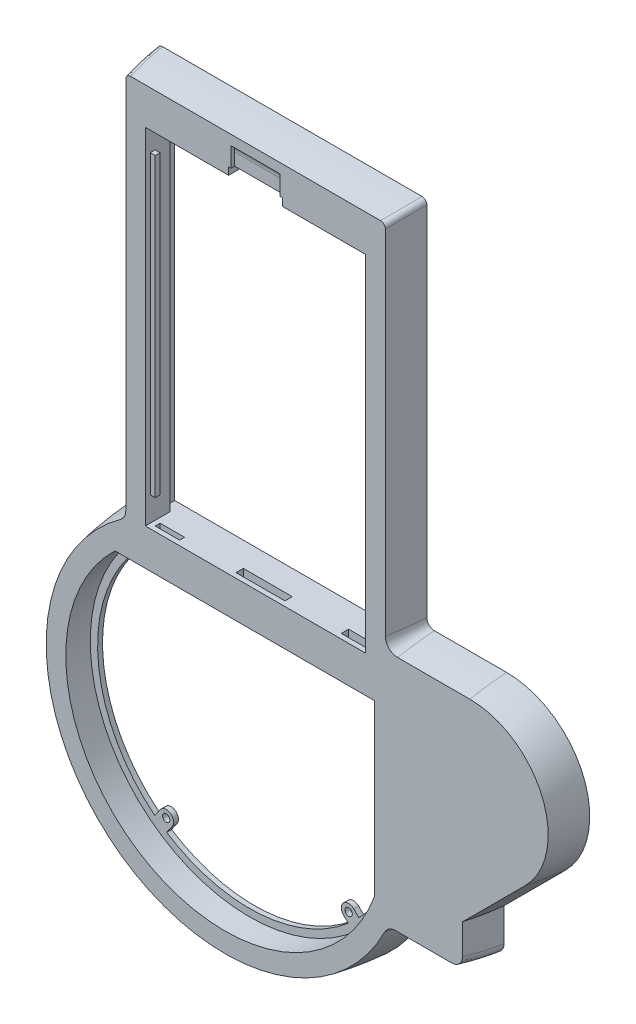
SolidWorks part; units mm, degrees
ref_plane "前视基准面" through (0, 0, 0) normal (0, 0, 1) x (1, 0, 0)
ref_plane "上视基准面" through (0, 0, 0) normal (0, 1, 0) x (1, 0, 0)
ref_plane "右视基准面" through (0, 0, 0) normal (1, 0, 0) x (0, 0, -1)
sketch "Sketch1" plane through (0, 0, 0) normal (0, 0, 1) x (1, 0, 0)
  line L0 (-10.9179, 60) -> (113.3582, 60) construction
  line L3 (-33.1662, 50) -> (-60, 50)
  line L4 (-60, 0) -> (-60, 50)
  line L6 (56.8821, -30) -> (90, -30)
  line L7 (90, -10.3553) -> (117.6777, 17.3223)
  line L13 (0, 60) -> (100, 60)
  line L14 (76, 5.7859) -> (76, -20.6668) construction
  line L16 (72, 20) -> (80, 20)
  line L17 (72, 20) -> (72, -20)
  line L18 (72, -20) -> (80, -20)
  line L19 (80, 20) -> (80, -20)
  line L20 (72, 20) -> (80, -20) construction
  line L21 (72, -20) -> (80, 20) construction
  line L25 (90, -30) -> (90, -10.3553)
  line L26 (56.8821, -30) -> (51.9615, -30)
  line L27 (57.5629, -26) -> (85.1685, -26) construction
  arc A0 (0, 60) -> (51.9615, -30) centre (0, 0) ccw
  circle A2 centre (0, 0) radius 10.5
  arc A8 (117.6777, 17.3223) -> (100, 60) centre (100, 35) ccw
  circle A9 centre (100, 35) radius 5
  circle A11 centre (69, -26) radius 1.5
  circle A12 centre (83, -26) radius 1.5
  point P21 (76, 0)
  dimension "D1" = 120
  dimension "D2" = 90
  dimension "D3" = 21
  dimension "D5" = 50
  dimension "D4" = 100
  dimension "D6" = 10
  dimension "D12" = 7
  dimension "D7" = 10
  dimension "D8" = 8
  dimension "D9" = 40
  dimension "D10" = 150
  dimension "D11" = 6
extrude "Boss-Extrude1" add sketch "Sketch1" along normal blind 2
sketch "Sketch2" plane through (0, 0, 2) normal (0, 0, 1) x (1, 0, 0)
  line L1 (-60, 0) -> (-60, 50) construction
  line L2 (0, 60) -> (100, 60) construction
  circle A1 centre (0, 0) radius 57
  circle A2 centre (60, 45) radius 2
  circle A6 centre (100, 35) radius 14
  dimension "D1" = 15
  dimension "D5" = 28
  dimension "D2" = 120
extrude "Cut-Extrude1" cut sketch "Sketch2" against normal up to next
sketch "Sketch3" plane through (0, 0, 0) normal (0, 0, -1) x (-1, 0, 0)
  line L4 (-30, 0) -> (-30, 80)
  line L5 (-30, 80) -> (5, 80)
  line L6 (5, 80) -> (5, 48)
  line L7 (5, 48) -> (25.3049, 16.1141)
  circle A2 centre (0, 0) radius 10.5
  arc A4 (-30, 0) -> (25.3049, 16.1141) centre (0, 0) ccw
  dimension "D1" = 80
  dimension "D2" = 35
  dimension "D3" = 32
extrude "Boss-Extrude2" add sketch "Sketch3" against normal blind 2
sketch "Sketch5" plane through (0, 0, 2) normal (0, 0, 1) x (1, 0, 0)
  line L0 (100, 48.4826) -> (100, 24.1919) construction
  line L1 (89.5844, 35) -> (110.5191, 35) construction
  circle A0 centre (92, 43) radius 2
  circle A1 centre (108, 43) radius 2
  circle A2 centre (108, 27) radius 2
  circle A3 centre (92, 27) radius 2
  dimension "D1" = 8
  dimension "D2" = 8
extrude "Cut-Extrude2" cut sketch "Sketch5" against normal blind 10
sketch "Sketch6" plane through (0, 0, 2) normal (0, 0, 1) x (1, 0, 0)
  line L0 (12.5, 60) -> (12.5, 200) construction
  line L1 (30, 80) -> (-5, 80) construction
  line L2 (12.5, 60) -> (55, 60)
  line L3 (-30, 60) -> (-30, 200)
  line L4 (-30, 200) -> (55, 200)
  line L5 (55, 60) -> (55, 200)
  line L6 (-30, 60) -> (55, 200) construction
  line L7 (-30, 200) -> (55, 60) construction
  line L8 (-30, 60) -> (-30, 51.9615)
  line L9 (12.5, 60) -> (-5, 60)
  line L10 (-5, 80) -> (-5, 59.7913) construction
  line L11 (-5, 60) -> (-5, 59.7913)
  arc A0 (-5, 59.7913) -> (-33.1662, 50) centre (0, 0) ccw construction
  arc A1 (-5, 59.7913) -> (-30, 51.9615) centre (0, 0) ccw
  point P2 (12.5, 130)
  point P10 (12.5, 80)
  dimension "D1" = 85
extrude "Boss-Extrude4" add sketch "Sketch6" against normal up to surface (2 mm away) up to face at (94, 27, 0)
sketch "Sketch7" plane through (0, 0, 2) normal (0, 0, 1) x (1, 0, 0)
  line L0 (55, 130) -> (-30, 130) construction
  line L1 (55, 60) -> (55, 200) construction
  line L2 (-30, 200) -> (-30, 51.9615) construction
  line L3 (12.5, 200) -> (12.5, 60) construction
  line L4 (55, 200) -> (-30, 200) construction
  circle A0 centre (-24, 194.5) radius 2
  circle A1 centre (49, 194.5) radius 2
  circle A2 centre (49, 65.5) radius 2
  circle A3 centre (-24, 65.5) radius 2
  circle A4 centre (-24, 130) radius 2
  circle A5 centre (49, 130) radius 2
  dimension "D1" = 4
  dimension "D2" = 4
  dimension "D3" = 6
  dimension "D4" = 5.5
  dimension "D5" = 5.5
  dimension "D6" = 6
extrude "Cut-Extrude3" cut sketch "Sketch7" against normal blind 10
sketch "Sketch8" plane through (0, 0, 2) normal (0, 0, 1) x (1, 0, 0)
  circle A0 centre (0, 0) radius 65
  circle A1 centre (0, 0) radius 10.5
extrude "Boss-Extrude5" add sketch "Sketch8" against normal up to surface (2 mm away) up to face at (51, 194.5, 0)
sketch "Sketch9" plane through (0, 0, 2) normal (0, 0, 1) x (1, 0, 0)
  line L0 (-60, 50) -> (-60, 25)
  line L1 (-60, 50) -> (-41.5331, 50)
  arc A0 (-41.5331, 50) -> (-60, 25) centre (0, 0) ccw
extrude "Cut-Extrude4" cut sketch "Sketch9" against normal blind 10
sketch "Sketch10" plane through (0, 0, 2) normal (0, 0, 1) x (1, 0, 0)
  line L0 (12.5, 200) -> (12.5, 60) construction
  line L1 (55, 200) -> (-30, 200) construction
  line L2 (55, 60) -> (100, 60) construction
  line L3 (-37.5, 210) -> (62.5, 210)
  line L4 (-37.5, 210) -> (-37.5, 60)
  line L5 (-37.5, 60) -> (62.5, 60)
  line L6 (62.5, 210) -> (62.5, 60)
  line L7 (-37.5, 210) -> (62.5, 60) construction
  line L8 (-37.5, 60) -> (62.5, 210) construction
  line L10 (-30, 200) -> (55, 200)
  line L11 (-30, 200) -> (-30, 60)
  line L12 (-30, 60) -> (55, 60)
  line L13 (55, 200) -> (55, 60)
  point P4 (12.5, 135)
  dimension "D1" = 100
  dimension "D2" = 150
extrude "Boss-Extrude6" add sketch "Sketch10" against normal blind 4 contours L4 L3 L6 L5 | L11 L10 L13 L12
sketch "Sketch11" plane through (0, 0, 2) normal (0, 0, 1) x (1, 0, 0)
  line L0 (-37.5, 60) -> (-37.5, 59.108)
  line L1 (-37.5, 60) -> (-36.0555, 60)
  line L2 (-30, 60) -> (-30, 57.6628)
  line L3 (-37.5, 60) -> (-30, 60) construction
  line L4 (-36.0555, 60) -> (-30, 60)
  line L5 (-30, 60) -> (-30, 57.6628)
  line L6 (63.2456, -30) -> (57.6628, -30)
  line L7 (90, -30) -> (57.6628, -30) construction
  arc A0 (-37.5, 59.108) -> (63.2456, -30) centre (0, 0) ccw
  arc A1 (-30, 57.6628) -> (57.6628, -30) centre (0, 0) ccw
  line M7 (-37.5, 60) -> (-30, 60)
  line M8 (-30, 60) -> (-30, 57.6628)
  arc M9 (-30, 57.6628) -> (57.6628, -30) centre (0, 0) ccw
  line M10 (57.6628, -30) -> (90, -30)
extrude "Boss-Extrude7" add sketch "Sketch11" against normal blind 4 contours L0 A0 M10 M9 M8 M7
sketch "Sketch12" plane through (0, 0, 2) normal (0, 0, 1) x (1, 0, 0)
  line L0 (95, -5.3553) -> (90, -10.3553)
  line L1 (62.5, 64) -> (100, 64)
  line L2 (94, -12.0122) -> (120.5061, 14.4939)
  line L4 (90, -10.3553) -> (117.6777, 17.3223) construction
  line L5 (90, -10.3553) -> (90, -30)
  line L6 (90, -30) -> (63.2456, -30)
  line L8 (97.8284, -8.1838) -> (94, -12.0122)
  line L9 (94, -12.0122) -> (94, -30)
  line L10 (90, -30) -> (94, -30)
  line L11 (62.5, 60) -> (100, 60)
  line L12 (62.5, 64) -> (62.5, 60)
  line L13 (92.8284, -13.1838) -> (120.5061, 14.4939) construction
  line L14 (94, -12.0122) -> (94, -34) construction
  line L16 (90, -10.3553) -> (117.6777, 17.3223)
  line L17 (94, -34) -> (63.2456, -34) construction
  arc A0 (120.5061, 14.4939) -> (100, 64) centre (100, 35) ccw
  arc A3 (117.6777, 17.3223) -> (100, 60) centre (100, 35) ccw construction
  arc A6 (117.6777, 17.3223) -> (100, 60) centre (100, 35) ccw
  dimension "D1" = 4
extrude "Boss-Extrude8" add sketch "Sketch12" against normal blind 4
sketch "Sketch13" plane through (0, 0, 2) normal (0, 0, 1) x (1, 0, 0)
  line L1 (0, 60) -> (100, 60)
  line L2 (56.8821, -30) -> (90, -30) construction
  line L3 (56.8821, -30) -> (51.9615, -30) construction
  line L4 (90, -30) -> (90, -10.3553) construction
  line L5 (90, -10.3553) -> (117.6777, 17.3223) construction
  line L6 (56.8821, -30) -> (90, -30)
  line L7 (63.2456, -30) -> (94, -30)
  line L8 (94, -30) -> (94, -12.0122)
  line L9 (94, -30) -> (94, -12.0122)
  line L10 (94, -12.0122) -> (120.5061, 14.4939)
  line L11 (62.5, 64) -> (62.5, 210)
  line L12 (62.5, 210) -> (-37.5, 210)
  line L13 (-37.5, 210) -> (-37.5, 59.108)
  line L14 (63.2456, -30) -> (94, -30)
  line L18 (62.5, 64) -> (62.5, 210)
  line L19 (62.5, 210) -> (-37.5, 210)
  line L20 (-37.5, 210) -> (-37.5, 59.108)
  line L21 (56.8821, -30) -> (51.9615, -30)
  line L22 (90, -30) -> (90, -10.3553)
  line L23 (90, -10.3553) -> (117.6777, 17.3223)
  line L30 (94, -12.0122) -> (120.5061, 14.4939)
  line L31 (100, 64) -> (62.5, 64)
  line L32 (100, 64) -> (62.5, 64)
  arc A0 (0, 60) -> (51.9615, -30) centre (0, 0) ccw construction
  arc A1 (0, 60) -> (51.9615, -30) centre (0, 0) ccw
  arc A2 (120.5061, 14.4939) -> (100, 64) centre (100, 35) ccw
  arc A3 (-37.5, 59.108) -> (63.2456, -30) centre (0, 0) ccw
  arc A5 (-37.5, 59.108) -> (63.2456, -30) centre (0, 0) ccw
  arc A6 (117.6777, 17.3223) -> (100, 60) centre (100, 35) ccw construction
  arc A7 (117.6777, 17.3223) -> (100, 60) centre (100, 35) ccw
  arc A10 (120.5061, 14.4939) -> (100, 64) centre (100, 35) ccw
  line M17 (63.2456, -30) -> (94, -30)
  circle M32 centre (92, 27) radius 2
  circle M33 centre (108, 27) radius 2
  circle M34 centre (108, 43) radius 2
  circle M35 centre (92, 43) radius 2
  circle M36 centre (60, 45) radius 2
  line M37 (72, 20) -> (80, 20)
  line M38 (80, 20) -> (80, -20)
  line M39 (80, -20) -> (72, -20)
  line M40 (72, -20) -> (72, 20)
  circle M41 centre (100, 35) radius 5
  circle M42 centre (69, -26) radius 1.5
  circle M43 centre (83, -26) radius 1.5
  circle M44 centre (0, 0) radius 10.5
  dimension "D1" = 0
extrude "Cut-Extrude5" cut sketch "Sketch13" against normal blind 4 contours L23 A7 L1 A1 L21 L6 L22 M17 M33 M35 M40 M37 M38 M39 M41 M43 M44 M42 M36 M34 M32 | M37 M40 M39 M38 | M35 | M34 | M41 | M33 | M32 | M36 | M44
sketch "Sketch14" plane through (0, 0, 2) normal (0, 0, 1) x (1, 0, 0)
  line L0 (94, -12.0122) -> (94, -30) construction
  line L1 (94, -12.0122) -> (120.5061, 14.4939) construction
  line L2 (62.5, 64) -> (100, 64) construction
  line L3 (94, -12.0122) -> (94, -30)
  line L4 (94, -12.0122) -> (120.5061, 14.4939)
  line L5 (62.5, 64) -> (100, 64)
  line L6 (60.5, 62) -> (60.5, 62)
  line L7 (60.5, 62) -> (60.5, 62)
  line L8 (60.5, 62) -> (60.5, 62)
  line L9 (60.5, 62) -> (60.5, 62)
  line L10 (60.5, 62) -> (60.5, 62)
  line L11 (60.5, 62) -> (60.5, 62)
  line L12 (60.5, 62) -> (60.5, 62)
  line L13 (60.5, 62) -> (100, 62)
  line L14 (92, -11.1838) -> (119.0919, 15.9081)
  line L15 (92, -11.1838) -> (92, -30)
  line L16 (60.5, 64) -> (60.5, 62)
  line L17 (92, -30) -> (94, -30)
  line L52 (60.5, 208) -> (-35.5, 208)
  line L53 (60.5, 64) -> (60.5, 208)
  line L54 (-35.5, 208) -> (-35.5, 57.9978)
  line L55 (60.5, 208) -> (-35.5, 208)
  line L56 (60.5, 64) -> (60.5, 208)
  line L57 (-35.5, 208) -> (-35.5, 57.9978)
  line L71 (62.5, 210) -> (62.5, 64) construction
  line L72 (-37.5, 210) -> (62.5, 210) construction
  line L73 (-37.5, 210) -> (-37.5, 59.108) construction
  line L77 (62.5, 210) -> (62.5, 64)
  line L78 (-37.5, 210) -> (62.5, 210)
  line L79 (-37.5, 210) -> (-37.5, 59.108)
  line L80 (63.2456, -30) -> (61.0246, -30)
  line L81 (56.8821, -30) -> (90, -30) construction
  arc A0 (120.5061, 14.4939) -> (100, 64) centre (100, 35) ccw construction
  arc A1 (120.5061, 14.4939) -> (100, 64) centre (100, 35) ccw
  arc A2 (60.5, 62) -> (60.5, 62) centre (60.5, 62) ccw
  arc A3 (60.5, 62) -> (60.5, 62) centre (60.5, 62) cw
  arc A4 (119.0919, 15.9081) -> (100, 62) centre (100, 35) ccw
  arc A19 (-35.5, 57.9978) -> (61.4385, -29.1429) centre (0, 0) ccw
  arc A20 (-35.5, 57.9978) -> (61.0246, -30) centre (0, 0) ccw
  arc A26 (-37.5, 59.108) -> (63.2456, -30) centre (0, 0) ccw construction
  arc A28 (-37.5, 59.108) -> (63.2456, -30) centre (0, 0) ccw
  dimension "D1" = 2
  dimension "D2" = 2
extrude "Boss-Extrude9" add sketch "Sketch14" along normal blind 35
sketch "Sketch15" plane through (0, 0, 2) normal (0, 0, 1) x (1, 0, 0)
  line L0 (12.5, 208) -> (12.5, 61.1759) construction
  line L1 (-35.5, 208) -> (60.5, 208) construction
  line L2 (0, 60) -> (100, 60) construction
  line L3 (-30, 200) -> (55, 200) construction
  line L4 (-30, 200) -> (-30, 60) construction
  line L5 (-30, 60) -> (55, 60) construction
  line L6 (55, 200) -> (55, 60) construction
  line L7 (-30, 200) -> (55, 60) construction
  line L8 (-30, 60) -> (55, 200) construction
  line L10 (-30, 203) -> (55, 203) construction
  line L11 (-30, 203) -> (-30, 67) construction
  line L12 (-30, 67) -> (55, 67) construction
  line L13 (55, 203) -> (55, 67) construction
  line L14 (-30, 203) -> (55, 67) construction
  line L15 (-30, 67) -> (55, 203) construction
  line L16 (-17.5, 64) -> (42.5, 64)
  line L17 (-17.5, 64) -> (-17.5, 61.7752)
  line L18 (-17.5, 61.7752) -> (42.5, 61.7752)
  line L19 (42.5, 64) -> (42.5, 61.7752)
  line L20 (-17.5, 64) -> (42.5, 61.7752) construction
  line L21 (-17.5, 61.7752) -> (42.5, 64) construction
  point P4 (12.5, 130)
  point P11 (12.5, 135)
  point P16 (12.5, 62.8876)
  dimension "D1" = 85
  dimension "D2" = 140
  dimension "D3" = 85
  dimension "D4" = 136
  dimension "D5" = 5
  dimension "D6" = 3
  dimension "D7" = 60
extrude "Boss-Extrude10" add sketch "Sketch15" along normal blind 35
sketch "Sketch16" plane through (0, 0, 2) normal (0, 0, 1) x (1, 0, 0)
  line L1 (-35.5, 208) -> (60.5, 208) construction
  line L2 (42.5, 64) -> (-17.5, 64) construction
  line L3 (-35.5, 208) -> (60.5, 208) construction
  line L4 (-15.5, 208) -> (-10.5, 208)
  line L5 (-15.5, 208) -> (-15.5, 163)
  line L6 (-15.5, 64) -> (-10.5, 64)
  line L7 (-10.5, 208) -> (-10.5, 163)
  line L8 (-17.5, 64) -> (-17.5, 61.7752) construction
  line L9 (10, 208) -> (15, 208)
  line L10 (10, 208) -> (10, 163)
  line L11 (10, 64) -> (15, 64)
  line L12 (15, 208) -> (15, 163)
  line L13 (35.5, 208) -> (40.5, 208)
  line L14 (35.5, 208) -> (35.5, 163)
  line L15 (35.5, 64) -> (40.5, 64)
  line L16 (40.5, 208) -> (40.5, 163)
  line L17 (42.5, 61.7752) -> (42.5, 64) construction
  line L18 (-35.5, 57.9978) -> (-35.5, 208) construction
  line L19 (-35.5, 163) -> (-15.5, 163)
  line L20 (-35.5, 163) -> (-35.5, 158)
  line L21 (-35.5, 158) -> (-15.5, 158)
  line L22 (60.5, 163) -> (60.5, 158)
  line L23 (60.5, 208) -> (60.5, 62) construction
  line L24 (60.5, 208) -> (60.5, 62) construction
  line L25 (-35.5, 114) -> (-15.5, 114)
  line L26 (-35.5, 114) -> (-35.5, 109)
  line L27 (-35.5, 109) -> (-15.5, 109)
  line L28 (60.5, 114) -> (60.5, 109)
  line L29 (-15.5, 158) -> (-15.5, 114)
  line L30 (-10.5, 158) -> (-10.5, 114)
  line L31 (-10.5, 163) -> (10, 163)
  line L32 (-10.5, 158) -> (10, 158)
  line L33 (12.5, 163) -> (35.5, 163)
  line L34 (15, 158) -> (35.5, 158)
  line L36 (10, 158) -> (10, 114)
  line L37 (15, 158) -> (15, 114)
  line L38 (35.5, 158) -> (35.5, 114)
  line L39 (40.5, 158) -> (40.5, 114)
  line L40 (40.5, 163) -> (60.5, 163)
  line L41 (40.5, 158) -> (60.5, 158)
  line L42 (40.5, 114) -> (60.5, 114)
  line L43 (40.5, 109) -> (60.5, 109)
  line L44 (-15.5, 109) -> (-15.5, 64)
  line L45 (-10.5, 109) -> (-10.5, 64)
  line L46 (10, 109) -> (10, 64)
  line L47 (15, 109) -> (15, 64)
  line L48 (35.5, 109) -> (35.5, 64)
  line L49 (40.5, 109) -> (40.5, 64)
  line L50 (-10.5, 114) -> (10, 114)
  line L51 (-10.5, 109) -> (10, 109)
  line L52 (15, 114) -> (35.5, 114)
  line L53 (15, 109) -> (35.5, 109)
  dimension "D9" = 45
  dimension "D1" = 5
  dimension "D2" = 5
  dimension "D4" = 5
  dimension "D5" = 2
  dimension "D6" = 2
  dimension "D7" = 5
  dimension "D8" = 5
  dimension "D10" = 45
extrude "Boss-Extrude12" add sketch "Sketch16" along normal blind 5
sketch "Sketch17" plane through (0, 0, 7) normal (0, 0, 1) x (1, 0, 0)
  line L0 (40.5, 163) -> (60.5, 163) construction
  line L1 (53.5, 163) -> (60.5, 163)
  line L2 (53.5, 163) -> (53.5, 158)
  line L3 (53.5, 158) -> (60.5, 158)
  line L4 (60.5, 163) -> (60.5, 158)
  line L5 (55, 200) -> (55, 60) construction
  line L6 (-35.5, 158) -> (-15.5, 158) construction
  line L7 (-35.5, 163) -> (-28.5, 163)
  line L8 (-35.5, 163) -> (-35.5, 158)
  line L9 (-35.5, 158) -> (-28.5, 158)
  line L10 (-28.5, 163) -> (-28.5, 158)
  line L11 (-35.5, 109) -> (-15.5, 109) construction
  line L12 (-35.5, 114) -> (-28.5, 114)
  line L13 (-35.5, 114) -> (-35.5, 109)
  line L14 (-35.5, 109) -> (-28.5, 109)
  line L15 (-28.5, 114) -> (-28.5, 109)
  line L16 (40.5, 114) -> (60.5, 114) construction
  line L17 (53.5, 114) -> (60.5, 114)
  line L18 (53.5, 114) -> (53.5, 109)
  line L19 (53.5, 109) -> (60.5, 109)
  line L20 (60.5, 114) -> (60.5, 109)
  line L21 (40.5, 109) -> (60.5, 109) construction
  line L22 (40.5, 109) -> (60.5, 109) construction
  line L23 (-30, 200) -> (-30, 60) construction
  line L24 (-10.5, 109) -> (-10.5, 64) construction
  line L25 (-15.5, 64) -> (-10.5, 64)
  line L26 (-15.5, 64) -> (-15.5, 69.5)
  line L27 (-15.5, 69.5) -> (-10.5, 69.5)
  line L28 (-10.5, 64) -> (-10.5, 69.5)
  line L29 (-30, 67) -> (55, 67) construction
  line L30 (10, 109) -> (10, 64) construction
  line L31 (10, 69.5) -> (15, 69.5)
  line L32 (10, 69.5) -> (10, 64)
  line L33 (10, 64) -> (15, 64)
  line L34 (15, 69.5) -> (15, 64)
  line L35 (35.5, 109) -> (35.5, 64) construction
  line L36 (35.5, 69.5) -> (40.5, 69.5)
  line L37 (35.5, 69.5) -> (35.5, 64)
  line L38 (35.5, 64) -> (40.5, 64)
  line L39 (40.5, 69.5) -> (40.5, 64)
  line L40 (-10.5, 208) -> (-10.5, 163) construction
  line L41 (-15.5, 208) -> (-10.5, 208)
  line L42 (-15.5, 208) -> (-15.5, 201.5)
  line L43 (-15.5, 201.5) -> (-10.5, 201.5)
  line L44 (-10.5, 208) -> (-10.5, 201.5)
  line L45 (-30, 203) -> (55, 203) construction
  line L46 (10, 208) -> (10, 163) construction
  line L47 (10, 201.5) -> (15, 201.5)
  line L48 (10, 201.5) -> (10, 208)
  line L49 (10, 208) -> (15, 208)
  line L50 (15, 201.5) -> (15, 208)
  line L51 (35.5, 208) -> (35.5, 163) construction
  line L52 (35.5, 201.5) -> (40.5, 201.5)
  line L53 (35.5, 201.5) -> (35.5, 208)
  line L54 (35.5, 208) -> (40.5, 208)
  line L55 (40.5, 201.5) -> (40.5, 208)
  dimension "D1" = 1.5
  dimension "D2" = 1.5
  dimension "D3" = 1.5
  dimension "D4" = 2.5
  dimension "D5" = 1.5
extrude "Boss-Extrude13" add sketch "Sketch17" along normal up to surface (30 mm away) up to face at (52.7768, 54.128, 37)
sketch "Sketch18" plane through (0, 109, 0) normal (0, -1, 0) x (1, 0, 0)
  line L0 (55.51, 37) -> (55.51, 9)
  line L1 (53.5, 37) -> (60.5, 37) construction
  line L2 (53.51, 7) -> (53.5, 7)
  line L3 (53.5, 37) -> (53.5, 7) construction
  line L4 (53.5, 7) -> (53.5, 37)
  line L5 (53.5, 37) -> (55.51, 37)
  arc A0 (55.51, 9) -> (53.51, 7) centre (53.51, 9) cw
  dimension "D2" = 2
  dimension "D1" = 2.01
extrude "Cut-Extrude6" cut sketch "Sketch18" against normal up to surface (54 mm away)
ref_plane "Plane1" through (12.5, 0, 0) normal (-1, 0, 0) x (0, 0, 1)
mirror "Mirror1" about plane through (12.5, 0, 0) normal (-1, 0, 0) of "Cut-Extrude6"
sketch "Sketch19" plane through (12.5, 0, 0) normal (-1, 0, 0) x (0, 0, 1)
  line L0 (37, 203.51) -> (9, 203.51)
  line L1 (37, 208) -> (37, 201.5) construction
  line L2 (7, 201.51) -> (7, 201.5)
  line L3 (37, 201.5) -> (7, 201.5) construction
  line L4 (37, 203.51) -> (37, 201.5)
  line L5 (37, 201.5) -> (7, 201.5)
  line L6 (37, 66.49) -> (10, 66.49)
  line L7 (37, 69.5) -> (37, 64) construction
  line L8 (7, 69.49) -> (7, 69.5)
  line L9 (37, 69.5) -> (7, 69.5) construction
  line L10 (37, 66.49) -> (37, 69.5)
  line L11 (37, 69.5) -> (7, 69.5)
  arc A0 (9, 203.51) -> (7, 201.51) centre (9, 201.51) ccw
  arc A1 (10, 66.49) -> (7, 69.49) centre (10, 69.49) cw
  dimension "D2" = 2
  dimension "D4" = 3
  dimension "D1" = 2.01
  dimension "D3" = 3.01
extrude "Cut-Extrude7" cut sketch "Sketch19" against normal mid plane 60
sketch "Sketch20" plane through (0, 0, 2) normal (0, 0, 1) x (1, 0, 0)
  line L0 (0, 0) -> (30, -51.9615) construction
  line L1 (0, 0) -> (-30, 51.9615) construction
  line L2 (0, 0) -> (-51.9615, -30) construction
  line L3 (103.8388, 3.4835) -> (92.5257, 14.7966) construction
  line L4 (90, -10.3553) -> (117.6777, 17.3223) construction
  line L5 (-23.3689, 52.4761) -> (-4.9075, 20.5001) construction
  line L6 (-33.7612, 46.4761) -> (-20.1962, 22.9808)
  line L7 (-23.3689, 52.4761) -> (-24.6535, 54.7011)
  line L8 (-23.3689, 52.4761) -> (-9.8038, 28.9808)
  line L9 (-33.7612, 46.4761) -> (-35.0458, 48.7011)
  line L10 (23.3689, -52.4761) -> (24.6535, -54.7011)
  line L11 (33.7612, -46.4761) -> (35.0458, -48.7011)
  line L12 (33.7612, -46.4761) -> (20.1962, -22.9808)
  line L13 (23.3689, -52.4761) -> (9.8038, -28.9808)
  line L14 (-51.6041, -22.8654) -> (-28.9808, -9.8038)
  line L15 (-45.6041, -33.2577) -> (-22.9808, -20.1962)
  line L16 (-51.6041, -22.8654) -> (-54.7011, -24.6535)
  line L17 (-45.6041, -33.2577) -> (-48.7011, -35.0458)
  line L18 (98.8884, 12.6754) -> (105.9599, 5.6045)
  line L23 (94.6468, 8.434) -> (101.7175, 1.3618)
  line L28 (101.7175, 1.3618) -> (105.9599, 5.6045)
  arc A0 (0, 60) -> (51.9615, -30) centre (0, 0) ccw construction
  arc A1 (-20.1962, 22.9808) -> (-9.8038, 28.9808) centre (-15, 25.9808) ccw
  arc A2 (-22.9808, -20.1962) -> (-28.9808, -9.8038) centre (-25.9808, -15) ccw
  arc A3 (20.1962, -22.9808) -> (9.8038, -28.9808) centre (15, -25.9808) ccw
  arc A5 (-35.0458, 48.7011) -> (-24.6535, 54.7011) centre (0, 0) cw
  arc A6 (24.6535, -54.7011) -> (35.0458, -48.7011) centre (0, 0) ccw
  arc A7 (-48.7011, -35.0458) -> (-54.7011, -24.6535) centre (0, 0) cw
  circle A8 centre (-15, 25.9808) radius 1.5
  circle A9 centre (-25.9808, -15) radius 1.5
  circle A10 centre (15, -25.9808) radius 1.5
  circle A11 centre (96.7678, 10.5546) radius 1.5
  arc A12 (98.8884, 12.6754) -> (94.6468, 8.434) centre (96.7678, 10.5546) ccw
  dimension "D1" = 30
  dimension "D2" = 30
  dimension "D3" = 30
  dimension "D4" = 10
  dimension "D5" = 6
extrude "Boss-Extrude14" add sketch "Sketch20" against normal blind 2
ref_plane "Plane2" through (0, 0, 37) normal (0, 0, 1) x (1, 0, 0)
sketch "Sketch21" plane through (0, 0, 37) normal (0, 0, 1) x (1, 0, 0)
  line L0 (119.0919, 15.9081) -> (92, -11.1838) construction
  line L1 (-37.5, 210) -> (62.5, 210)
  line L2 (-37.5, 210) -> (-37.5, 64)
  line L4 (62.5, 210) -> (62.5, 64)
  line L5 (119.0919, 15.9081) -> (92, -11.1838)
  line L6 (60.5, 62) -> (-37.5, 62)
  line L7 (-44.4553, 47) -> (103.3162, 47) construction
  line L8 (-49.1426, 47) -> (70.5, 47)
  line L9 (70.5, 47) -> (70.5, -20.9358)
  line L10 (70.5, -30) -> (63.2456, -30)
  line L11 (70.5, -30) -> (92, -30)
  line L12 (70.5, 47) -> (70.5, 62)
  line L13 (70.5, -20.9358) -> (90, -20.9358)
  line L14 (90, -30) -> (90, -10.3553) construction
  line L15 (61.0246, -30) -> (61.0246, 47)
  line L16 (70.5, 47) -> (124.1868, 47)
  line L20 (55.51, 62) -> (60.5, 62)
  line L21 (63.2456, -30) -> (92, -30)
  line L22 (90, -20.9358) -> (92, -20.9358)
  line L23 (-35.5, 62) -> (-35.5, 208)
  line L24 (-35.5, 208) -> (60.5, 208)
  line L25 (60.5, 208) -> (60.5, 62)
  line L46 (35.5, 203.51) -> (40.5, 203.51)
  line L47 (40.5, 203.51) -> (40.5, 208)
  line L48 (40.5, 208) -> (60.5, 208)
  line L49 (60.5, 208) -> (60.5, 163)
  line L50 (60.5, 163) -> (55.51, 163)
  line L51 (55.51, 163) -> (55.51, 158)
  line L52 (55.51, 158) -> (60.5, 158)
  line L53 (60.5, 158) -> (60.5, 114)
  line L54 (60.5, 114) -> (55.51, 114)
  line L55 (55.51, 114) -> (55.51, 109)
  line L56 (55.51, 109) -> (60.5, 109)
  line L57 (60.5, 109) -> (60.5, 62)
  line L58 (60.5, 62) -> (100, 62)
  line L59 (119.0919, 15.9081) -> (92, -11.1838)
  line L60 (92, -11.1838) -> (92, -30)
  line L61 (92, -30) -> (94, -30)
  line L62 (94, -30) -> (94, -12.0122)
  line L63 (94, -12.0122) -> (120.5061, 14.4939)
  line L64 (100, 64) -> (62.5, 64)
  line L65 (62.5, 64) -> (62.5, 210)
  line L66 (62.5, 210) -> (-37.5, 210)
  line L67 (-37.5, 210) -> (-37.5, 59.108)
  line L68 (63.2456, -30) -> (61.0246, -30)
  line L69 (-35.5, 57.9978) -> (-35.5, 109)
  line L70 (-35.5, 109) -> (-30.51, 109)
  line L72 (-30.51, 114) -> (-35.5, 114)
  line L73 (-35.5, 114) -> (-35.5, 158)
  line L74 (-35.5, 158) -> (-30.51, 158)
  line L75 (-30.51, 109) -> (-30.51, 114)
  line L76 (-30.51, 163) -> (-35.5, 163)
  line L77 (-35.5, 163) -> (-35.5, 208)
  line L78 (-35.5, 208) -> (-15.5, 208)
  line L79 (-15.5, 208) -> (-15.5, 203.51)
  line L81 (-10.5, 203.51) -> (-10.5, 208)
  line L82 (-10.5, 208) -> (10, 208)
  line L83 (10, 208) -> (10, 203.51)
  line L84 (-30.51, 158) -> (-30.51, 163)
  line L85 (15, 203.51) -> (15, 208)
  line L86 (15, 208) -> (35.5, 208)
  line L87 (35.5, 208) -> (35.5, 203.51)
  line L100 (60.5, 62) -> (100, 62)
  line L101 (119.0919, 15.9081) -> (92, -11.1838)
  line L102 (92, -11.1838) -> (92, -20.9358)
  line L103 (92, -30) -> (94, -30)
  line L104 (94, -30) -> (94, -12.0122)
  line L105 (94, -12.0122) -> (120.5061, 14.4939)
  line L106 (100, 64) -> (62.5, 64)
  line L107 (62.5, 64) -> (62.5, 210)
  line L108 (62.5, 210) -> (-37.5, 210)
  line L109 (-37.5, 210) -> (-37.5, 59.108)
  line L110 (63.2456, -30) -> (61.0246, -30)
  line L111 (-35.5, 57.9978) -> (-35.5, 62)
  line L150 (-15.5, 203.51) -> (-10.5, 203.51)
  line L152 (10, 203.51) -> (15, 203.51)
  arc A0 (-35.5, 57.9978) -> (61.0246, -30) centre (0, 0) ccw construction
  arc A1 (-35.5, 57.9978) -> (61.0246, -30) centre (0, 0) ccw
  arc A4 (119.0919, 15.9081) -> (100, 62) centre (100, 35) ccw
  arc A5 (120.5061, 14.4939) -> (100, 64) centre (100, 35) ccw
  arc A6 (-37.5, 59.108) -> (63.2456, -30) centre (0, 0) ccw
  arc A7 (-35.5, 57.9978) -> (61.0246, -30) centre (0, 0) ccw
  arc A8 (119.0919, 15.9081) -> (100, 62) centre (100, 35) ccw
  arc A9 (120.5061, 14.4939) -> (100, 64) centre (100, 35) ccw
  arc A10 (-37.5, 59.108) -> (63.2456, -30) centre (0, 0) ccw
  arc A11 (-35.5, 57.9978) -> (61.0246, -30) centre (0, 0) ccw
  dimension "D2" = 15
  dimension "D4" = 9.0642
  dimension "D1" = 0
extrude "Boss-Extrude15" add sketch "Sketch21" along normal blind 5
sketch "Sketch22" plane through (0, 0, 37) normal (0, 0, 1) x (1, 0, 0)
  line L1 (-84.8585, 214.4586) -> (151.8728, 214.4586)
  line L2 (-84.8585, 214.4586) -> (-84.8585, -77.374)
  line L3 (-84.8585, -77.374) -> (151.8728, -77.374)
  line L4 (151.8728, 214.4586) -> (151.8728, -77.374)
extrude "Cut-Extrude9" cut sketch "Sketch22" against normal up to next
sketch "Sketch24" plane through (0, 0, 42) normal (0, 0, 1) x (1, 0, 0)
  line L0 (61.0246, 47) -> (61.0246, -30)
  line L1 (70.5, 47) -> (120.7846, 47)
  line L2 (70.5, 47) -> (124.1868, 47) construction
  line L3 (70.5, 47) -> (70.5, -20.9358)
  line L4 (70.5, -20.9358) -> (90.4645, -20.9358)
  line L5 (70.5, -20.9358) -> (92, -20.9358) construction
  line L6 (94, -30) -> (63.2456, -30) construction
  line L7 (94, -30) -> (94, -12.0122) construction
  line L8 (94, -12.0122) -> (120.5061, 14.4939) construction
  line L9 (55.5, 203) -> (55.5, 62)
  line L10 (-30.5, 62) -> (-30.5, 203)
  line L11 (-30.5, 203) -> (55.5, 203)
  line L12 (55.5, 203) -> (55.5, 62)
  line L13 (-30.5, 62) -> (-30.5, 203)
  line L14 (-30.5, 203) -> (55.5, 203)
  line L15 (100, 64) -> (62.5, 64) construction
  line L16 (62.5, 210) -> (62.5, 64) construction
  line L17 (-37.5, 210) -> (62.5, 210) construction
  line L18 (-37.5, 210) -> (-37.5, 59.108) construction
  line L19 (94, -30) -> (63.2456, -30)
  line L20 (94, -30) -> (94, -12.0122)
  line L21 (94, -12.0122) -> (120.5061, 14.4939)
  line L22 (100, 64) -> (62.5, 64)
  line L23 (62.5, 210) -> (62.5, 64)
  line L24 (-37.5, 210) -> (62.5, 210)
  line L25 (-37.5, 210) -> (-37.5, 59.108)
  line L26 (-30.5, 62) -> (55.5, 62)
  line L27 (90.4645, -8.4767) -> (116.9706, 18.0294)
  line L28 (61.0246, 47) -> (-44.8999, 47)
  line L29 (-49.1426, 47) -> (61.0246, 47) construction
  line L30 (90.4645, -20.9358) -> (90.4645, -8.4767)
  arc A0 (-37.5, 59.108) -> (63.2456, -30) centre (0, 0) ccw construction
  arc A1 (120.5061, 14.4939) -> (100, 64) centre (100, 35) ccw construction
  arc A2 (-37.5, 59.108) -> (63.2456, -30) centre (0, 0) ccw
  arc A3 (120.5061, 14.4939) -> (100, 64) centre (100, 35) ccw
  arc A4 (-44.8999, 47) -> (58.728, -27.8571) centre (0, 0) ccw
  arc A5 (116.9706, 18.0294) -> (120.7846, 47) centre (100, 35) ccw
  arc A6 (-44.8999, 47) -> (61.0246, -22.383) centre (0, 0) ccw
  arc A7 (-34.8214, 54.886) -> (58.728, -27.8571) centre (0, 0) ccw construction
  arc A8 (116.9706, 18.0294) -> (100, 59) centre (100, 35) ccw construction
  line M13 (70.5, -20.9358) -> (70.5, 47)
  line M14 (70.5, 47) -> (124.1868, 47)
  arc M15 (124.1868, 47) -> (119.0919, 15.9081) centre (100, 35) cw
  line M16 (119.0919, 15.9081) -> (92, -11.1838)
  line M17 (92, -11.1838) -> (92, -20.9358)
  line M18 (92, -20.9358) -> (70.5, -20.9358)
  line M19 (60.5, 208) -> (60.5, 62)
  line M20 (60.5, 62) -> (-35.5, 62)
  line M21 (-35.5, 62) -> (-35.5, 208)
  line M22 (-35.5, 208) -> (60.5, 208)
  line M23 (61.0246, 47) -> (61.0246, -30)
  arc M24 (61.0246, -30) -> (-49.1426, 47) centre (0, 0) cw
  line M25 (-49.1426, 47) -> (61.0246, 47)
  arc M26 (-37.5, 59.108) -> (63.2456, -30) centre (0, 0) ccw
  line M27 (63.2456, -30) -> (94, -30)
  line M28 (94, -30) -> (94, -12.0122)
  line M29 (94, -12.0122) -> (120.5061, 14.4939)
  arc M30 (120.5061, 14.4939) -> (100, 64) centre (100, 35) ccw
  line M31 (100, 64) -> (62.5, 64)
  line M32 (62.5, 64) -> (62.5, 210)
  line M33 (62.5, 210) -> (-37.5, 210)
  line M34 (-37.5, 210) -> (-37.5, 59.108)
  dimension "D1" = 5
  dimension "D2" = 5
extrude "Boss-Extrude16" add sketch "Sketch24" along normal blind 10 contours L13 L14 L12 M20 M19 M22 M21 | L0 M34 M26 M27 M28 M29 M30 M31 M32 M33 M25 M23 M24 M22 M19 M20 M21 M18 M13 M14 M15 M16 M17 | A6 A4 L0 M25 M24 | A5 L27 L30 M18 M17 M16 M15 M14 | L25 A2 L19 L20 L21 A3 L22 L23 L24
sketch "Sketch25" plane through (0, 0, 52) normal (0, 0, 1) x (1, 0, 0)
  line L0 (12.5, 210) -> (12.5, 255.076) construction
  line L1 (62.5, 210) -> (-37.5, 210) construction
  line L2 (-2.5, 225) -> (-2.5, 210)
  line L3 (-2.5, 210) -> (27.5, 210)
  line L4 (27.5, 210) -> (27.5, 225)
  arc A0 (27.5, 225) -> (-2.5, 225) centre (12.5, 225) ccw
  dimension "D1" = 15
extrude "Boss-Extrude17" add sketch "Sketch25" against normal blind 6
sketch "Sketch31" plane through (0, 0, 52) normal (0, 0, 1) x (1, 0, 0)
  circle A0 centre (12.5, 225) radius 12.5
extrude "Cut-Extrude11" cut sketch "Sketch31" against normal blind 3.5
sketch "Sketch32" plane through (0, 0, 48.5) normal (0, 0, 1) x (1, 0, 0)
  circle A0 centre (12.5, 225) radius 7.5
extrude "Cut-Extrude12" cut sketch "Sketch32" against normal up to next
sketch "Sketch33" plane through (0, 0, 48.5) normal (0, 0, 1) x (1, 0, 0)
  line L0 (12.5, 225) -> (12.5, 240) construction
  arc A0 (27.5, 225) -> (-2.5, 225) centre (12.5, 225) ccw construction
  circle A1 centre (12.5, 235.5) radius 1.1
  dimension "D1" = 10.5
extrude "Cut-Extrude13" cut sketch "Sketch33" against normal blind 3
ref_plane "Plane3" through (12.5, 0, 0) normal (-1, 0, 0) x (0, 0, 1)
sketch "Sketch36" plane through (0, 0, 52) normal (0, 0, 1) x (1, 0, 0)
  line L0 (94, -30) -> (97, -30)
  line L1 (66.5507, -30) -> (63.2456, -30)
  line L75 (-37.5, 210) -> (-37.5, 59.108) construction
  line L76 (63.2456, -30) -> (94, -30) construction
  line L77 (94, -30) -> (94, -12.0122) construction
  line L78 (94, -12.0122) -> (120.5061, 14.4939) construction
  line L79 (100, 64) -> (62.5, 64) construction
  line L80 (62.5, 64) -> (62.5, 210) construction
  line L81 (62.5, 210) -> (27.5, 210) construction
  line L82 (27.5, 210) -> (27.5, 225) construction
  line L83 (-2.5, 225) -> (-2.5, 210) construction
  line L84 (-2.5, 210) -> (-37.5, 210) construction
  line L85 (65.1153, -33) -> (97, -33)
  line L86 (97, -33) -> (97, -13.2548)
  line L87 (97, -13.2548) -> (122.6274, 12.3726)
  line L88 (100, 67) -> (65.5, 67)
  line L89 (65.5, 67) -> (65.5, 213)
  line L90 (65.5, 213) -> (30.5, 213)
  line L91 (30.5, 213) -> (30.5, 225)
  line L92 (-5.5, 225) -> (-5.5, 213)
  line L93 (-5.5, 213) -> (-40.5, 213)
  line L94 (-40.5, 213) -> (-40.5, 60.7351)
  line L96 (97, -30) -> (97, -13.2548)
  line L97 (97, -13.2548) -> (122.6274, 12.3726)
  line L98 (100, 67) -> (65.5, 67)
  line L99 (65.5, 67) -> (65.5, 213)
  line L100 (65.5, 213) -> (30.5, 213)
  line L103 (-5.5, 213) -> (-40.5, 213)
  line L104 (-40.5, 213) -> (-40.5, 60.7351)
  line L105 (-37.5, 210) -> (-37.5, 59.108)
  line L106 (63.2456, -30) -> (66.5507, -30)
  line L107 (94, -30) -> (94, -12.0122)
  line L108 (94, -12.0122) -> (120.5061, 14.4939)
  line L109 (100, 64) -> (62.5, 64)
  line L110 (62.5, 64) -> (62.5, 210)
  line L111 (62.5, 210) -> (27.5, 210)
  line L112 (27.5, 210) -> (27.5, 213)
  line L113 (-2.5, 213) -> (-2.5, 210)
  line L114 (-2.5, 210) -> (-37.5, 210)
  line L115 (-5.5, 213) -> (-2.5, 213)
  line L116 (30.5, 213) -> (27.5, 213)
  arc A0 (-40.5, 60.7351) -> (66.5507, -30) centre (0, 0) ccw
  arc A16 (-37.5, 59.108) -> (63.2456, -30) centre (0, 0) ccw construction
  arc A17 (120.5061, 14.4939) -> (100, 64) centre (100, 35) ccw construction
  arc A19 (-40.5, 60.7351) -> (65.1153, -33) centre (0, 0) ccw
  arc A20 (122.6274, 12.3726) -> (100, 67) centre (100, 35) ccw
  arc A21 (30.5, 225) -> (-5.5, 225) centre (12.5, 225) ccw
  arc A22 (-40.5, 60.7351) -> (65.1153, -33) centre (0, 0) ccw
  arc A23 (122.6274, 12.3726) -> (100, 67) centre (100, 35) ccw
  arc A25 (-37.5, 59.108) -> (63.2456, -30) centre (0, 0) ccw
  arc A26 (120.5061, 14.4939) -> (100, 64) centre (100, 35) ccw
  line M28 (-37.5, 210) -> (-37.5, 59.108)
  arc M29 (-37.5, 59.108) -> (63.2456, -30) centre (0, 0) ccw
  line M30 (63.2456, -30) -> (94, -30)
  line M39 (-2.5, 225) -> (-2.5, 210)
  line M40 (-2.5, 210) -> (-37.5, 210)
  dimension "D1" = 3
extrude "Boss-Extrude19" add sketch "Sketch36" against normal up to surface (15 mm away) contours L104 A0 L115 L103 M30 M29 M28 M40 M39 | L96 L97 A23 L98 L99 L100 L116 L112 L111 L110 L109 A26 L108 L107 L0
fillet "Fillet1" radius 5 7 edges at (-40.5, 60.7351, 44.5) (65.5, 67, 44.5) (65.5, 213, 44.5) (-40.5, 213, 44.5) (27.5, 213, 49) (-2.5, 213, 49) (66.5507, -30, 44.5)
sketch "Sketch37" plane through (0, 0, 42) normal (0, 0, -1) x (-1, 0, 0)
  line L0 (-70.5, 47) -> (-70.5, -20.9358) construction
  line L1 (-70.5, -20.9358) -> (-92, -20.9358) construction
  line L2 (-90.4645, -20.9358) -> (-90.4645, -8.4767) construction
  line L3 (-90.4645, -8.4767) -> (-116.9706, 18.0294) construction
  line L4 (-70.5, 47) -> (-124.1868, 47) construction
  line L5 (-70.5, 47) -> (-70.5, -20.9358)
  line L6 (-70.5, -20.9358) -> (-90.4645, -20.9358)
  line L7 (-90.4645, -20.9358) -> (-90.4645, -8.4767)
  line L8 (-90.4645, -8.4767) -> (-116.9706, 18.0294)
  line L9 (-70.5, 47) -> (-120.7846, 47)
  arc A0 (-120.7846, 47) -> (-116.9706, 18.0294) centre (-100, 35) ccw construction
  arc A1 (-120.7846, 47) -> (-116.9706, 18.0294) centre (-100, 35) ccw
extrude "Boss-Extrude20" add sketch "Sketch37" against normal up to surface (10 mm away) up to face at (34.4039, 117.1063, 52)
sketch "Sketch38" plane through (0, 0, 37) normal (0, 0, -1) x (-1, 0, 0)
  line L1 (-27.5, 210) -> (2.5, 210)
  line L2 (-27.5, 210) -> (-27.5, 213)
  line L3 (-27.5, 213) -> (2.5, 213)
  line L4 (2.5, 210) -> (2.5, 213)
extrude "Boss-Extrude21" add sketch "Sketch38" against normal up to surface (9 mm away) up to face at (13.6, 235.5, 46)
ref_plane "Plane4" through (0, 0, 37) normal (0, 0, -1) x (-1, 0, 0)
sketch "Sketch39" plane through (0, 0, 37) normal (0, 0, -1) x (-1, 0, 0)
  line L7 (35.5, 213) -> (-60.5, 213)
  line L9 (35.5, 213) -> (-60.5, 213)
  line L11 (-65.5, 208) -> (-65.5, 72)
  line L13 (40.5, 63.3542) -> (40.5, 208)
  line L20 (40.5, 63.3542) -> (40.5, 208)
  line L21 (-65.5, 208) -> (-65.5, 72)
  line L22 (-70.5, 67) -> (-100, 67)
  line L23 (-70.5, 67) -> (-100, 67)
  line L25 (-122.6274, 12.3726) -> (-97, -13.2548)
  line L27 (-122.6274, 12.3726) -> (-97, -13.2548)
  line L29 (-97, -30) -> (-69.7065, -30)
  line L30 (-97, -30) -> (-69.7065, -30)
  line L31 (-97, -13.2548) -> (-97, -30)
  line L33 (-97, -13.2548) -> (-97, -30)
  arc A4 (-60.5, 213) -> (-65.5, 208) centre (-60.5, 208) ccw
  arc A9 (40.5, 208) -> (35.5, 213) centre (35.5, 208) ccw
  arc A12 (-60.5, 213) -> (-65.5, 208) centre (-60.5, 208) ccw
  arc A13 (-70.5, 67) -> (-65.5, 72) centre (-70.5, 72) ccw
  arc A14 (-70.5, 67) -> (-65.5, 72) centre (-70.5, 72) ccw
  arc A15 (-100, 67) -> (-122.6274, 12.3726) centre (-100, 35) ccw
  arc A16 (-65.2382, -32.7564) -> (42.5833, 59.293) centre (0, 0) ccw
  arc A17 (40.5, 63.3542) -> (42.5833, 59.293) centre (45.5, 63.3542) ccw
  arc A18 (40.5, 208) -> (35.5, 213) centre (35.5, 208) ccw
  arc A25 (-65.2382, -32.7564) -> (42.5833, 59.293) centre (0, 0) ccw
  arc A26 (40.5, 63.3542) -> (42.5833, 59.293) centre (45.5, 63.3542) ccw
  arc A27 (-100, 67) -> (-122.6274, 12.3726) centre (-100, 35) ccw
  arc A32 (-65.2382, -32.7564) -> (-69.7065, -30) centre (-69.7065, -35) ccw
  arc A33 (-65.2382, -32.7564) -> (-69.7065, -30) centre (-69.7065, -35) ccw
  dimension "D1" = 0
extrude "Boss-Extrude22" add sketch "Sketch39" along normal blind 39
ref_plane "Plane5" through (0, 0, 25) normal (0, 0, 1) x (1, 0, 0)
sketch "Sketch40" plane through (0, 0, 25) normal (0, 0, 1) x (1, 0, 0)
  line L7 (60.5, 213) -> (-35.5, 213)
  line L9 (60.5, 213) -> (-35.5, 213)
  line L11 (65.5, 72) -> (65.5, 208)
  line L13 (-40.5, 208) -> (-40.5, 63.3542)
  line L20 (-40.5, 208) -> (-40.5, 63.3542)
  line L21 (65.5, 72) -> (65.5, 208)
  line L22 (100, 67) -> (70.5, 67)
  line L23 (100, 67) -> (70.5, 67)
  line L25 (97, -13.2548) -> (122.6274, 12.3726)
  line L27 (97, -13.2548) -> (122.6274, 12.3726)
  line L29 (97, -30) -> (97, -13.2548)
  line L31 (69.7065, -30) -> (97, -30)
  line L32 (69.7065, -30) -> (97, -30)
  line L33 (97, -30) -> (97, -13.2548)
  arc A4 (65.5, 208) -> (60.5, 213) centre (60.5, 208) ccw
  arc A9 (-35.5, 213) -> (-40.5, 208) centre (-35.5, 208) ccw
  arc A12 (65.5, 208) -> (60.5, 213) centre (60.5, 208) ccw
  arc A13 (65.5, 72) -> (70.5, 67) centre (70.5, 72) ccw
  arc A14 (65.5, 72) -> (70.5, 67) centre (70.5, 72) ccw
  arc A15 (122.6274, 12.3726) -> (100, 67) centre (100, 35) ccw
  arc A16 (-42.5833, 59.293) -> (65.2382, -32.7564) centre (0, 0) ccw
  arc A17 (-42.5833, 59.293) -> (-40.5, 63.3542) centre (-45.5, 63.3542) ccw
  arc A18 (-35.5, 213) -> (-40.5, 208) centre (-35.5, 208) ccw
  arc A25 (-42.5833, 59.293) -> (65.2382, -32.7564) centre (0, 0) ccw
  arc A26 (-42.5833, 59.293) -> (-40.5, 63.3542) centre (-45.5, 63.3542) ccw
  arc A27 (122.6274, 12.3726) -> (100, 67) centre (100, 35) ccw
  arc A32 (69.7065, -30) -> (65.2382, -32.7564) centre (69.7065, -35) ccw
  arc A33 (69.7065, -30) -> (65.2382, -32.7564) centre (69.7065, -35) ccw
  dimension "D1" = 0
sketch "Sketch41" plane through (12.5, 0, 0) normal (-1, 0, 0) x (0, 0, 1)
  line L0 (-2, 213) -> (52, 213)
  arc A0 (-2, 213) -> (52, 213) centre (25, 65.45) cw
sweep "Sweep1" add profiles "Sketch41" path "Sketch40"
sketch "Sketch42" plane through (0, 0, 37) normal (0, 0, -1) x (-1, 0, 0)
  line L1 (118.0701, -89.7165) -> (-176.5446, -89.7165)
  line L2 (118.0701, -89.7165) -> (118.0701, 261.605)
  line L3 (118.0701, 261.605) -> (-176.5446, 261.605)
  line L4 (-176.5446, -89.7165) -> (-176.5446, 261.605)
extrude "Cut-Extrude16" cut sketch "Sketch42" along normal blind 39
sketch "Sketch43" plane through (12.5, 0, 0) normal (-1, 0, 0) x (0, 0, 1)
  line L0 (52, 213) -> (25.8111, 213) construction
  line L1 (37, 213) -> (46, 213) construction
  line L2 (37, 214.9692) -> (37, 208) construction
  line L3 (46, 213) -> (46, 213.9727)
  line L4 (46, 213.9727) -> (46, 215.1067)
  line L5 (46, 218) -> (46, 213.9727) construction
  line L6 (46, 215.1067) -> (37, 215.1067)
  line L7 (37, 215.1067) -> (37, 213)
  line L8 (37, 213) -> (46, 213)
extrude "Cut-Extrude17" cut sketch "Sketch43" against normal mid plane 30
fillet "Fillet2" radius 1 2 edges at (-2.5, 214.5389, 41.5075) (27.5, 214.5389, 41.5075)
fillet "Fillet3" radius 1 5 edges at (28.0381, 215.7435, 46) (27.5, 221.5, 46) (-3.0381, 215.7435, 46) (-2.5, 221.5, 46) (12.5, 240, 46)
ref_plane "Plane6" through (0, 0, 42) normal (0, 0, -1) x (-1, 0, 0)
sketch "Sketch44" plane through (0, 0, 42) normal (0, 0, -1) x (-1, 0, 0)
  line L0 (49.1426, 47) -> (-61.0246, 47) construction
  line L2 (38.8999, 42) -> (38.8999, 47)
  line L3 (44.0147, 39.8722) -> (50.1277, 45.9479)
  line L4 (38.8999, 47) -> (49.1426, 47)
  arc A0 (38.8999, 42) -> (44.0147, 39.8722) centre (41.8999, 42) ccw
  arc A2 (-61.0246, -30) -> (49.1426, 47) centre (0, 0) ccw construction
  circle A3 centre (41.8999, 42) radius 1.5
  arc A4 (50.1277, 45.9479) -> (49.1426, 47) centre (0, 0) ccw
  dimension "D1" = 5
  dimension "D2" = 3
extrude "Boss-Extrude23" add sketch "Sketch44" along normal blind 2
sketch "Sketch45" plane through (0, 0, 42) normal (0, 0, -1) x (-1, 0, 0)
  line L0 (44.8999, 47) -> (-61.0246, 47) construction
  line L1 (-61.0246, 47) -> (-61.0246, -22.383) construction
  line L2 (-53.0246, 42) -> (-53.0246, 47)
  line L3 (-56.0246, 39) -> (-61.0246, 39)
  line L4 (-61.0246, 39) -> (-61.0246, 47)
  line L5 (-61.0246, 47) -> (-53.0246, 47)
  arc A0 (-56.0246, 39) -> (-53.0246, 42) centre (-56.0246, 42) ccw
  circle A1 centre (-56.0246, 42) radius 1.5
  dimension "D1" = 5
  dimension "D2" = 5
extrude "Boss-Extrude24" add sketch "Sketch45" along normal blind 2
sketch "Sketch46" plane through (0, 0, 42) normal (0, 0, -1) x (-1, 0, 0)
  line L5 (35.5, 62) -> (-60.5, 62) construction
  line L6 (-70.5, 47) -> (-70.5, -20.9358) construction
  line L9 (-40.5, -43) -> (-44.6949, -47.1949) construction
  line L12 (-42.6213, -40.8787) -> (-48.9467, -47.204)
  line L13 (-38.3787, -45.1213) -> (-44.5936, -51.3362)
  line L14 (50.1277, 45.9479) -> (47.9981, 43.8313)
  line L15 (-61.0246, -22.383) -> (-61.0246, -30)
  line L16 (50.1277, 45.9479) -> (47.9981, 43.8313)
  arc A6 (-61.0246, -22.383) -> (47.9981, 43.8313) centre (0, 0) ccw construction
  arc A7 (-38.3787, -45.1213) -> (-42.6213, -40.8787) centre (-40.5, -43) ccw
  arc A8 (-61.0246, -30) -> (50.1277, 45.9479) centre (0, 0) ccw construction
  arc A9 (-61.0246, -22.383) -> (47.9981, 43.8313) centre (0, 0) ccw
  arc A10 (-61.0246, -30) -> (50.1277, 45.9479) centre (0, 0) ccw
  arc A12 (-47.8935, -48.2722) -> (-45.717, -50.3384) centre (0, 0) ccw
  arc A13 (-48.9467, -47.204) -> (-44.5936, -51.3362) centre (0, 0) ccw
  arc A14 (-43.5932, -48.2145) -> (47.9981, 43.8313) centre (0, 0) ccw
  circle A15 centre (-40.5, -43) radius 1.5
  dimension "D1" = 105
  dimension "D3" = 0
  dimension "D2" = 30
extrude "Boss-Extrude26" add sketch "Sketch46" along normal blind 2
sketch "Sketch47" plane through (0, 0, 42) normal (0, 0, -1) x (-1, 0, 0)
  line L0 (49.1426, 47) -> (-61.0246, 47) construction
  line L1 (-61.0246, -30) -> (-61.0246, 47) construction
  line L2 (31.5118, -48.7119) -> (37.2116, -56.9148)
  line L3 (36.4391, -45.2881) -> (42.0843, -53.4126)
  arc A0 (36.4391, -45.2881) -> (31.5118, -48.7119) centre (33.9754, -47) ccw
  arc A1 (-61.0246, -30) -> (49.1426, 47) centre (0, 0) ccw construction
  arc A2 (-44.5936, -51.3362) -> (50.1277, 45.9479) centre (0, 0) ccw construction
  arc A3 (37.2116, -56.9148) -> (42.0843, -53.4126) centre (0, 0) ccw
  circle A4 centre (33.9754, -47) radius 1.5
  dimension "D1" = 94
  dimension "D2" = 95
extrude "Boss-Extrude27" add sketch "Sketch47" along normal blind 2
sketch "Sketch48" plane through (0, 0, 42) normal (0, 0, -1) x (-1, 0, 0)
  line L0 (-61.0246, -30) -> (-61.0246, 47) construction
  line L1 (49.1426, 47) -> (-61.0246, 47) construction
  line L2 (-61.0246, -30) -> (-61.0246, 39)
  line L3 (38.8999, 47) -> (-53.0246, 47)
  line L4 (38.8999, 44) -> (-53.0246, 44)
  line L5 (-58.0246, -21.8437) -> (-58.0246, 39)
  line L6 (-53.0246, 47) -> (-53.0246, 44)
  line L7 (-53.0246, 42) -> (-53.0246, 47) construction
  line L8 (-61.0246, 39) -> (-58.0246, 39)
  line L9 (-61.0246, 39) -> (-56.0246, 39) construction
  line L10 (38.8999, 47) -> (38.8999, 44)
  line L11 (38.8999, 47) -> (38.8999, 42) construction
  line L12 (50.1277, 45.9479) -> (47.9981, 43.8313)
  line L13 (42.0843, -53.4126) -> (40.3693, -50.9443)
  line L15 (-48.9467, -47.204) -> (-46.825, -45.0824)
  line L16 (-42.6213, -40.8787) -> (-48.9467, -47.204) construction
  line L18 (47.8435, 44) -> (-58.0246, 44) construction
  line L19 (49.1426, 47) -> (-61.0246, 47) construction
  line L20 (-58.0246, -29.2942) -> (-58.0246, 44) construction
  line L21 (-61.0246, -30) -> (-61.0246, 47) construction
  line L22 (40.3693, -50.9443) -> (38.6538, -48.4756)
  line L23 (47.9981, 43.8313) -> (45.8683, 41.7145)
  line L24 (48.0129, 48.0757) -> (43.7963, 43.8849) construction
  line L25 (44.0147, 39.8722) -> (50.1277, 45.9479) construction
  line L26 (40.3693, -50.9443) -> (38.6538, -48.4756)
  line L27 (42.0843, -53.4126) -> (36.4391, -45.2881) construction
  line L28 (-40.6589, -46.8066) -> (-44.5936, -51.3362)
  line L29 (33.9282, -51.8929) -> (37.2116, -56.9148)
  line L30 (39.6207, -55.1245) -> (36.2616, -50.2901) construction
  line L31 (-46.825, -45.0824) -> (-44.6638, -43.0016)
  arc A0 (-61.0246, -30) -> (49.1426, 47) centre (0, 0) ccw construction
  arc A1 (42.0843, -53.4126) -> (50.1277, 45.9479) centre (0, 0) ccw construction
  arc A2 (-61.0246, -30) -> (-48.9467, -47.204) centre (0, 0) ccw
  arc A3 (42.0843, -53.4126) -> (50.1277, 45.9479) centre (0, 0) ccw
  arc A6 (-58.0246, -29.2942) -> (47.8435, 44) centre (0, 0) ccw construction
  arc A8 (-61.0246, -30) -> (49.1426, 47) centre (0, 0) ccw construction
  arc A9 (42.0843, -53.4126) -> (50.1277, 45.9479) centre (0, 0) ccw
  arc A11 (38.6538, -48.4756) -> (45.8683, 41.7145) centre (0, 0) ccw
  arc A12 (36.2616, -50.2901) -> (43.7963, 43.8849) centre (0, 0) ccw construction
  arc A13 (40.3693, -50.9443) -> (47.9981, 43.8313) centre (0, 0) ccw construction
  arc A14 (-44.5936, -51.3362) -> (37.2116, -56.9148) centre (0, 0) ccw
  arc A15 (-40.6589, -46.8066) -> (33.9282, -51.8929) centre (0, 0) ccw
  arc A16 (-55.3465, -27.9421) -> (-44.6638, -43.0016) centre (0, 0) ccw
  arc A18 (-58.0246, -21.8437) -> (-44.6638, -43.0016) centre (0, 0) ccw
  arc A19 (-40.6589, -46.8066) -> (45.8683, 41.7145) centre (0, 0) ccw
  dimension "D1" = 3
  dimension "D2" = 3
  dimension "D3" = 6
extrude "Boss-Extrude28" add sketch "Sketch48" along normal blind 2
sketch "Sketch49" plane through (12.5, 0, 0) normal (-1, 0, 0) x (0, 0, 1)
  line L0 (37, 214.9692) -> (37, 240.8646)
  line L1 (37, 240.8646) -> (52, 240.8646)
  line L2 (52, 240.8646) -> (52, 213)
  arc A0 (52, 213) -> (37, 214.9692) centre (25, 65.45) ccw construction
  arc A1 (52, 213) -> (37, 214.9692) centre (25, 65.45) ccw
extrude "Cut-Extrude18" cut sketch "Sketch49" against normal through all both and the other way through all
ref_plane "Plane7" through (0, 203, 0) normal (0, -1, 0) x (-1, 0, 0)
sketch "Sketch52" plane through (0, 203, 0) normal (0, -1, 0) x (-1, 0, 0)
  line L0 (-65.5, -52) -> (40.5, -52)
  line L1 (-67.4692, -37) -> (42.4692, -37)
  arc A0 (40.5, -52) -> (42.4692, -37) centre (-107.05, -25) ccw construction
  arc A1 (-67.4692, -37) -> (-65.5, -52) centre (82.05, -25) ccw construction
  arc A2 (40.5, -52) -> (42.4692, -37) centre (-107.05, -25) ccw
  arc A3 (-67.4692, -37) -> (-65.5, -52) centre (82.05, -25) ccw
extrude "Boss-Extrude30" add sketch "Sketch52" against normal blind 15
sketch "Sketch54" plane through (0, 0, 52) normal (0, 0, 1) x (1, 0, 0)
  line L1 (-30.5, 203) -> (-32.5, 203)
  line L2 (-30.5, 203) -> (-30.5, 62)
  line L3 (-30.5, 62) -> (-32.5, 62)
  line L4 (-32.5, 203) -> (-32.5, 62)
  line L5 (55.5, 203) -> (57.5, 203)
  line L6 (55.5, 203) -> (55.5, 62)
  line L7 (55.5, 62) -> (57.5, 62)
  line L8 (57.5, 203) -> (57.5, 62)
  dimension "D1" = 2
  dimension "D2" = 2
extrude "Cut-Extrude20" cut sketch "Sketch54" against normal up to next
sketch "Sketch57" plane through (0, 203, 0) normal (0, -1, 0) x (1, 0, 0)
  line L0 (12.5, 52) -> (12.5, 37) construction
  line L1 (-32.5, 52) -> (57.5, 52) construction
  line L2 (-35.5, 37) -> (60.5, 37) construction
  line L4 (23.5, 52) -> (1.5, 52)
  line L5 (23.5, 52) -> (23.5, 37)
  line L6 (23.5, 37) -> (1.5, 37)
  line L7 (1.5, 52) -> (1.5, 37)
  line L8 (23.5, 52) -> (1.5, 37) construction
  line L9 (23.5, 37) -> (1.5, 52) construction
  point P6 (12.5, 44.5)
  dimension "D1" = 22
extrude "Cut-Extrude22" cut sketch "Sketch57" against normal blind 3
sketch "Sketch58" plane through (0, 206, 0) normal (0, -1, 0) x (1, 0, 0)
  line L0 (1.5, 52) -> (1.5, 37) construction
  line L1 (2.5, 49) -> (22.5, 49)
  line L2 (2.5, 49) -> (2.5, 48)
  line L3 (2.5, 48) -> (22.5, 48)
  line L4 (22.5, 49) -> (22.5, 48)
  line L5 (23.5, 52) -> (1.5, 52) construction
  line L6 (1.5, 48) -> (23.5, 48) construction
  line L7 (1.5, 52) -> (1.5, 37) construction
  line L8 (23.5, 37) -> (23.5, 52) construction
  dimension "D1" = 20
  dimension "D2" = 1
  dimension "D3" = 1
  dimension "D4" = 3
revolve "Cut-Revolve2" cut sketch "Sketch58" angle 360 about L6
sketch "Sketch59" plane through (0, 206, 0) normal (0, -1, 0) x (1, 0, 0)
  line L0 (23.5, 52) -> (1.5, 52) construction
  line L1 (2.5, 52) -> (22.5, 52)
  line L2 (2.5, 52) -> (2.5, 50.5)
  line L3 (2.5, 50.5) -> (22.5, 50.5)
  line L4 (22.5, 52) -> (22.5, 50.5)
  dimension "D1" = 1.5
extrude "Cut-Extrude23" cut sketch "Sketch59" against normal blind 5
sketch "Sketch60" plane through (-32.5, 0, 0) normal (1, 0, 0) x (0, 0, -1)
  line L0 (-52, 203) -> (-52, 62) construction
  line L1 (-50, 72) -> (-48, 72)
  line L2 (-50, 72) -> (-50, 193)
  line L3 (-50, 193) -> (-48, 193)
  line L4 (-48, 72) -> (-48, 193)
  line L5 (-42, 62) -> (-52, 62) construction
  line L6 (-42, 203) -> (-52, 203) construction
  dimension "D1" = 2
  dimension "D2" = 2
  dimension "D3" = 10
  dimension "D4" = 10
extrude "Boss-Extrude31" add sketch "Sketch60" along normal blind 2
mirror "Mirror3" about plane through (12.5, 0, 0) normal (-1, 0, 0) of "Boss-Extrude31"
sketch "Sketch61" plane through (0, 62, 0) normal (0, 1, 0) x (1, 0, 0)
  line L0 (12.5, -52) -> (12.5, -37) construction
  line L1 (22.5, -50) -> (2.5, -50)
  line L2 (22.5, -50) -> (22.5, -47)
  line L3 (22.5, -47) -> (2.5, -47)
  line L4 (2.5, -50) -> (2.5, -47)
  line L5 (22.5, -50) -> (2.5, -47) construction
  line L6 (22.5, -47) -> (2.5, -50) construction
  line L7 (57.5, -52) -> (-32.5, -52) construction
  line L8 (-35.5, -37) -> (60.5, -37) construction
  line L10 (55.5, -50) -> (45.5, -50)
  line L11 (55.5, -50) -> (55.5, -47)
  line L12 (55.5, -47) -> (45.5, -47)
  line L13 (45.5, -50) -> (45.5, -47)
  line L14 (-30.5, -50) -> (-20.5, -50)
  line L15 (-30.5, -50) -> (-30.5, -48)
  line L16 (-30.5, -48) -> (-20.5, -48)
  line L17 (-20.5, -50) -> (-20.5, -48)
  point P0 (12.5, -48.5)
  dimension "D1" = 20
  dimension "D2" = 3
  dimension "D3" = 10
  dimension "D4" = 2
  dimension "D5" = 10
  dimension "D6" = 3
  dimension "D7" = 10
  dimension "D8" = 2
extrude "Cut-Extrude24" cut sketch "Sketch61" against normal blind 3
sketch "Sketch62" plane through (12.5, 0, 0) normal (-1, 0, 0) x (0, 0, 1)
  line L0 (52, 211) -> (50.5, 211) construction
  line L1 (50.5, 211) -> (50.5, 206) construction
  line L2 (52, 218) -> (52, 63.3542) construction
  line L3 (50.5, 211) -> (52, 211)
  line L4 (52, 211) -> (52, 214)
  arc A0 (50.5, 211) -> (52, 214) centre (54.1001, 211.075) cw
  dimension "D1" = 3
extrude "Cut-Extrude25" cut sketch "Sketch62" against normal mid plane 20
sketch "Sketch63" plane through (0, 0, 37) normal (0, 0, -1) x (-1, 0, 0)
  line L0 (42.4692, 218) -> (42.4692, 63.3542) construction
  line L1 (-67.4692, 218) -> (42.4692, 218)
  line L2 (-67.4692, 218) -> (-67.4692, 185.121)
  line L3 (-67.4692, 185.121) -> (42.4692, 185.121)
  line L4 (42.4692, 218) -> (42.4692, 185.121)
extrude "Boss-Extrude32" add sketch "Sketch63" along normal blind 40
sketch "Sketch64" plane through (0, 0, 37) normal (0, 0, -1) x (-1, 0, 0)
  line L0 (-67.4692, 218) -> (42.4692, 218)
sketch "Sketch65" plane through (12.5, 0, 0) normal (-1, 0, 0) x (0, 0, 1)
  line L0 (52, 218) -> (-3, 218)
  arc A0 (52, 218) -> (-3, 218) centre (24.5, 70.5424) ccw
sweep "Sweep2" add profiles "Sketch65" path "Sketch64"
sketch "Sketch66" plane through (0, 185.121, 0) normal (0, -1, 0) x (1, 0, 0)
  line L0 (65.5, 52) -> (75.0529, 52)
  line L1 (75.0529, 52) -> (75.0529, -5.6992)
  line L2 (75.0529, -5.6992) -> (-47.8484, -5.6992)
  line L3 (-47.8484, -5.6992) -> (-47.8484, 52)
  line L4 (-47.8484, 52) -> (-40.5, 52)
  line L5 (-42.4692, 37) -> (67.4692, 37)
  arc A0 (-40.5, 52) -> (-42.4692, 37) centre (107.05, 25) ccw construction
  arc A1 (67.4692, 37) -> (65.5, 52) centre (-82.05, 25) ccw construction
  arc A2 (-40.5, 52) -> (-42.4692, 37) centre (107.05, 25) ccw
  arc A3 (67.4692, 37) -> (65.5, 52) centre (-82.05, 25) ccw
extrude "Cut-Extrude26" cut sketch "Sketch66" against normal up to next
fillet "Fillet4" radius 2 2 edges
fillet "Fillet6" radius 4.5 1 edges at (98.1738, -31.1738, 44.5248)
ref_plane "Plane8" through (0, 0, 37) normal (0, 0, -1) x (-1, 0, 0)
